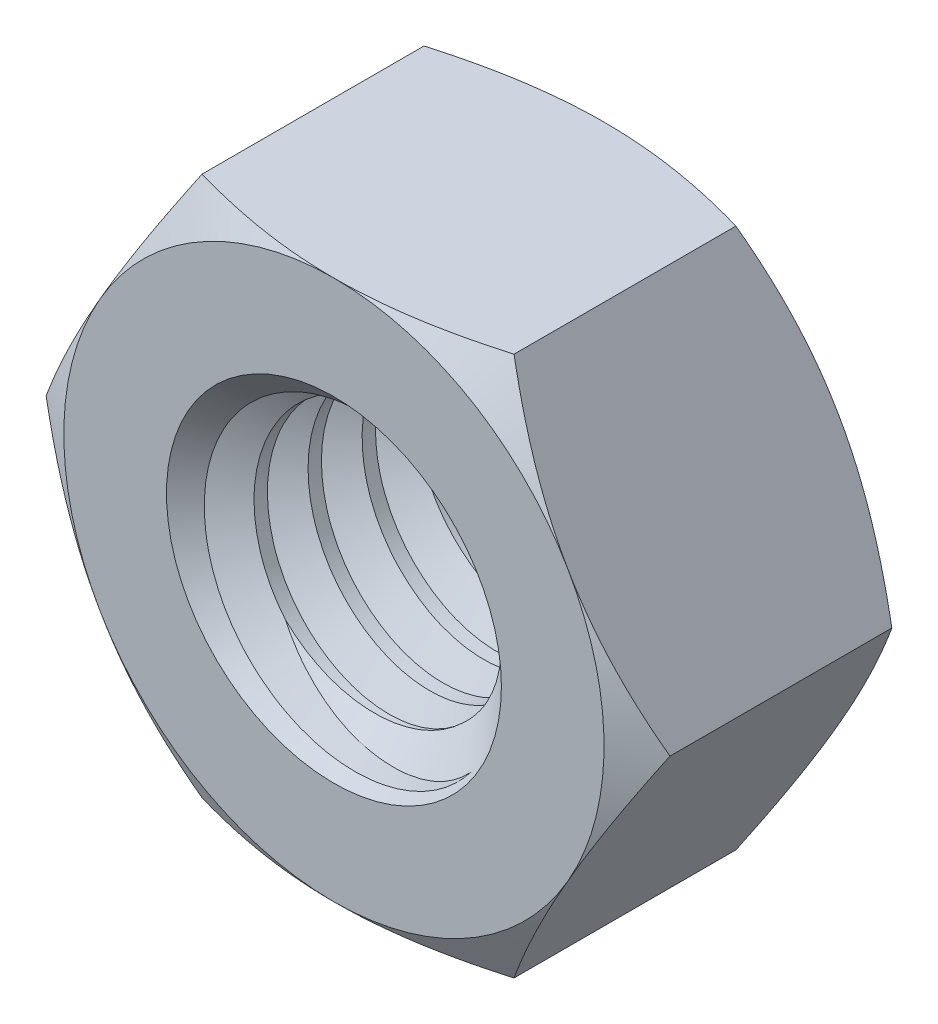
SolidWorks part; units mm, degrees
ref_plane "Front" through (0, 0, 0) normal (0, 0, 1) x (1, 0, 0)
ref_plane "Top" through (0, 0, 0) normal (0, 1, 0) x (1, 0, 0)
ref_plane "Right" through (0, 0, 0) normal (1, 0, 0) x (0, 0, -1)
sketch "Çizim1" plane through (0, 0, 0) normal (0, 0, 1) x (1, 0, 0)
  line L1 (5.7735, 0) -> (2.8868, 5)
  line L2 (2.8868, 5) -> (-2.8868, 5)
  line L3 (-2.8868, 5) -> (-5.7735, 0)
  line L4 (-5.7735, 0) -> (-2.8868, -5)
  line L5 (-2.8868, -5) -> (2.8868, -5)
  line L6 (2.8868, -5) -> (5.7735, 0)
  circle A0 centre (0, 0) radius 5 construction
  point P1 (0, 0)
  dimension "D1" = 10
extrude "Yükseklik-Ekstrüzyon1" add sketch "Çizim1" along normal blind 5
sketch "Çizim2" plane through (0, 0, 5) normal (0, 0, 1) x (1, 0, 0)
  circle A0 centre (0, 0) radius 5
extrude "Kes-Ekstrüzyon1" cut sketch "Çizim2" against normal blind 5 draft 60 flip side to cut
sketch "Çizim3" plane through (0, 0, 0) normal (0, 0, -1) x (-1, 0, 0)
  circle A0 centre (0, 0) radius 5
  dimension "D1" = 10
extrude "Kes-Ekstrüzyon2" cut sketch "Çizim3" against normal blind 5 draft 60 flip side to cut
sketch "Çizim4" plane through (0, 0, 0) normal (0, 0, -1) x (-1, 0, 0)
  circle A0 centre (0, 0) radius 2.35
  dimension "D1" = 4.7
extrude "Kes-Ekstrüzyon3" cut sketch "Çizim4" against normal blind 5
chamfer "Pah1" distance 0.75 angle 45 2 edges at (-2.35, 0, 0) (-2.35, 0, 5)
sketch "Çizim5" plane through (0, 0, 0) normal (0, 0, -1) x (-1, 0, 0)
  circle A0 centre (0, 0) radius 2.35
curve "Helis/Spiral1" pitch 1 height 6 radius 2.35 centre (0, 0, 0) axis (0, 0, 1) start towards (1, 0, 0)
ref_plane "Düzlem1" through (2.35, 0, 6) normal (0, 0.9977, 0.0676) x (1, 0, 0)
sketch "Çizim6" plane through (2.35, 0, 6) normal (0, 0.9977, 0.0676) x (1, 0, 0)
  line L1 (0.65, 0) -> (-0.1939, 0.4872)
  line L3 (-0.1939, -0.4872) -> (0.65, 0)
  line L4 (-0.1939, 0.4872) -> (-0.1939, -0.4872)
  line L5 (-0.325, 0.5629) -> (-0.325, 0) [skipped]
  circle A0 centre (0, 0) radius 0.325 construction
  dimension "D1" = 0.65
sweep "Kes-Süpür1" cut profiles "Çizim6" path "Helis/Spiral1" align with end faces yes
